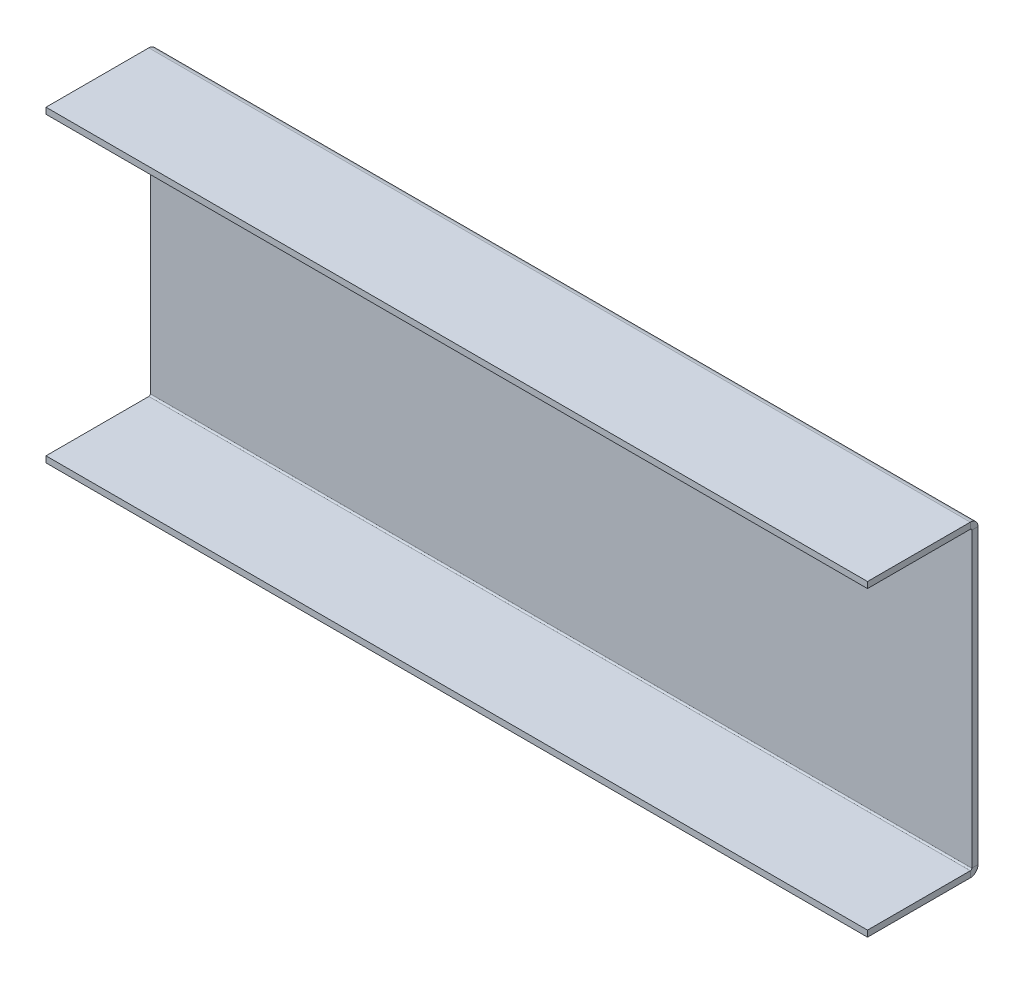
SolidWorks part; units mm, degrees
note: The reader was unsure of these and kept them because the rebuilt part matched: flange length of "Edge-Flange1", "Edge-Flange2".
material "AISI 316 Stainless Steel Sheet (SS)"
ref_plane "Front Plane" through (0, 0, 0) normal (0, 0, 1) x (1, 0, 0)
ref_plane "Top Plane" through (0, 0, 0) normal (0, 1, 0) x (1, 0, 0)
ref_plane "Right Plane" through (0, 0, 0) normal (1, 0, 0) x (0, 0, -1)
sketch "Sketch1" plane through (0, 0, 0) normal (0, 0, 1) x (1, 0, 0)
  line L1 (-200, 75) -> (200, 75)
  line L2 (-200, 75) -> (-200, -75)
  line L3 (-200, -75) -> (200, -75)
  line L4 (200, 75) -> (200, -75)
  line L5 (-200, 75) -> (200, -75) construction
  line L6 (-200, -75) -> (200, 75) construction
  point P0 (0, 0)
  dimension "D1" = 150
  dimension "D2" = 400
base flange "Base-Flange1" sketch "Sketch1" thickness 3 reverse thickness direction no parameters "D1"=0.7366
edge flange "Edge-Flange1" sketch "Sketch8" flange angle 90 flange length 50.8 flange position material inside bend radius 0.7366 thickness 3 relief rectangular parameters "D6"=10
sketch "Sketch8" plane through (0, -75, 0) normal (0, -1, 0) x (1, 0, 0)
  line L2 (-200, 0) -> (-200, 50.8)
  line L3 (-200, 50.8) -> (200, 50.8)
  line L4 (200, 50.8) -> (200, 0)
  line L7 (-200, 0) -> (200, 0) construction
  line L8 (-200, 0) -> (200, 0)
bend "EdgeBend1" bend radius 0.7366 bend angle 90 parameters "D5"=1
edge flange "Edge-Flange2" sketch "Sketch11" flange angle 90 flange length 50.8 flange position material inside bend radius 0.7366 thickness 3 relief rectangular parameters "D6"=10
sketch "Sketch11" plane through (0, 75, 0) normal (0, 1, 0) x (-1, 0, 0)
  line L0 (-200, 0) -> (200, 0) construction
  line L1 (-200, 0) -> (200, 0)
  line L2 (-200, 0) -> (-200, 50.8)
  line L3 (-200, 50.8) -> (200, 50.8)
  line L4 (200, 50.8) -> (200, 0)
bend "EdgeBend2" bend radius 0.7366 bend angle 90 parameters "D5"=2
sketch "Bend-Lines1" [suppressed] plane through (0, 0, 0) normal (0, 1, 0) x (1, 0, 0)
sketch "Bounding-Box1" [suppressed] plane through (0, 0, 0) normal (0, 1, 0) x (1, 0, 0)
sheet metal parameters "Sheet-Metal2" thickness 3 parameters "D1"=0.7366
flat pattern "Flat-Pattern2" [suppressed]
sketch "Bend-Lines2" plane through (0, 0, 0) normal (0, 1, 0) x (1, 0, 0)
sketch3d "Bounding-Box2" [suppressed]
  line L0 (225, -75, 0) -> (-225, -75, 0) construction
  line L1 (225, 75, 0) -> (-225, 75, 0) construction
  line L2 (225, -75, 0) -> (225, 75, 0) construction
  line L3 (-225, -75, 0) -> (-225, 75, 0) construction
sheet metal parameters "Sheet-Metal3" thickness 3 parameters "D1"=0.7366
flat pattern "Flat-Pattern2"
sketch "Bend-Lines2" plane through (0, 0, 0) normal (0, 0, 1) x (1, 0, 0)
  line L0 (-225, -73.02) -> (225, -73.02) construction
  line L1 (-225, -73.02) -> (225, -73.02) construction
sketch3d "Bounding-Box2" [suppressed]
  line L0 (-225, -147.04, 0) -> (225, -147.04, 0) construction
  line L1 (-225, 75, 0) -> (225, 75, 0) construction
  line L2 (-225, -147.04, 0) -> (-225, 75, 0) construction
  line L3 (225, -147.04, 0) -> (225, 75, 0) construction
bend of the flat pattern "Flatten-<EdgeBend1>1"
sheet metal parameters "Sheet-Metal4" thickness 3 parameters "D1"=0.7366
flat pattern "Flat-Pattern2"
sketch "Bend-Lines2" plane through (0, 0, 0) normal (0, 0, 1) x (1, 0, 0)
  line L0 (-200, -73.02) -> (200, -73.02) construction
  line L1 (-200, -73.02) -> (200, -73.02) construction
  line L2 (200, 73.02) -> (-200, 73.02) construction
  line L3 (200, 73.02) -> (-200, 73.02) construction
sketch3d "Bounding-Box2" [suppressed]
  line L0 (-200, -124.84, 0) -> (200, -124.84, 0) construction
  line L1 (-200, 124.84, 0) -> (200, 124.84, 0) construction
  line L2 (-200, -124.84, 0) -> (-200, 124.84, 0) construction
  line L3 (200, -124.84, 0) -> (200, 124.84, 0) construction
bend of the flat pattern "Flatten-<EdgeBend1>1"
bend of the flat pattern "Flatten-<EdgeBend2>1"
